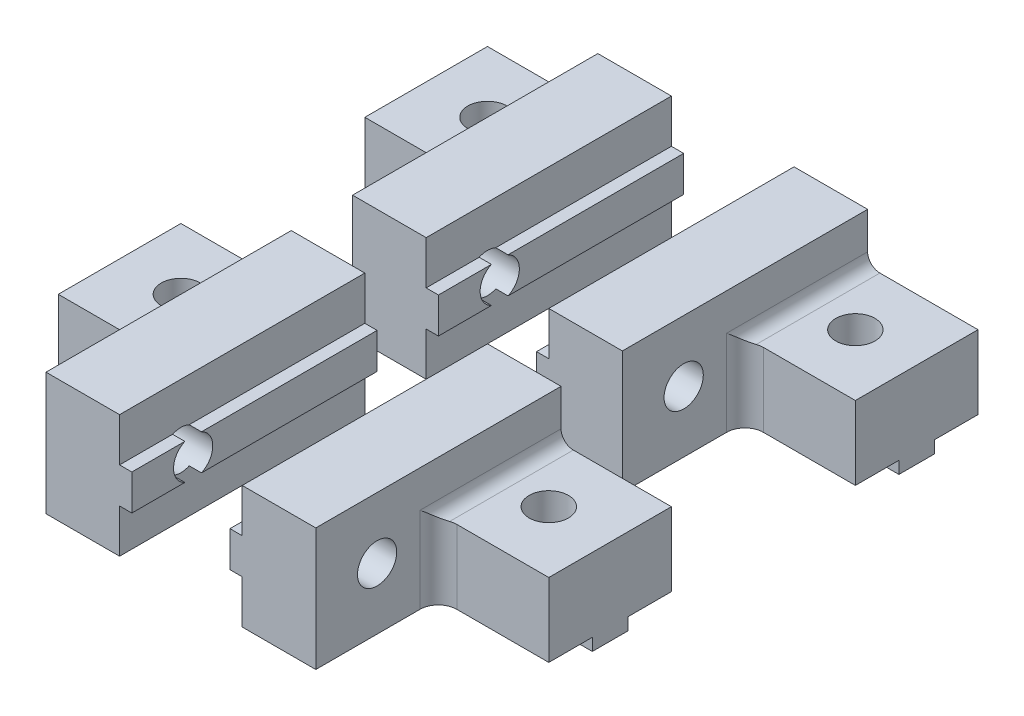
SolidWorks part; units mm, degrees
ref_plane "Front Plane" through (0, 0, 0) normal (0, 0, 1) x (1, 0, 0)
ref_plane "Top Plane" through (0, 0, 0) normal (0, 1, 0) x (1, 0, 0)
ref_plane "Right Plane" through (0, 0, 0) normal (1, 0, 0) x (0, 0, -1)
sketch "Esquisse1" plane through (0, 0, 0) normal (0, 0, 1) x (1, 0, 0)
  line L0 (0, 0) -> (15, 0)
  line L1 (15, 0) -> (15, 6)
  line L2 (15, 6) -> (7, 6)
  line L3 (6, 10) -> (6, 7)
  line L5 (6, 10) -> (0, 10)
  line L6 (0, 10) -> (0, 0)
  arc A0 (7, 6) -> (6, 7) centre (7, 7) cw
  point P5 (0, 0)
  point P9 (4.8458, 8.4496)
  dimension "D1" = 8
  dimension "D2" = 10
  dimension "D3" = 6
  dimension "D4" = 15
extrude "Main" add sketch "Esquisse1" along normal blind 20
sketch "Esquisse4" plane through (0, 0, 0) normal (-1, 0, 0) x (0, 0, 1)
  line L0 (20, 10) -> (0, 10) construction
  line L1 (0, 6.45) -> (20, 6.45)
  line L2 (0, 6.45) -> (0, 3.55)
  line L3 (0, 3.55) -> (20, 3.55)
  line L4 (20, 6.45) -> (20, 3.55)
  line L6 (0, 10) -> (0, 0) construction
  line L7 (20, 10) -> (20, 0) construction
  dimension "D1" = 2.9
  dimension "D2" = 3.55
extrude "VerticalGuidance" add sketch "Esquisse4" along normal blind 1
sketch "Esquisse2" plane through (0, 0, 0) normal (-1, 0, 0) x (0, 0, 1)
  line L0 (20, 10) -> (20, 6.45) construction
  line L5 (20, 0) -> (0, 0) construction
  circle A0 centre (15, 5) radius 1.6
  dimension "D1" = 3.2
  dimension "D2" = 5
  dimension "D3" = 5
extrude "VerticalHole" cut sketch "Esquisse2" against normal through all both and the other way through all
sketch "Esquisse5" plane through (0, 0, 0) normal (0, -1, 0) x (-1, 0, 0)
  line L1 (0, -3.55) -> (-15, -3.55)
  line L2 (0, -3.55) -> (0, -6.45)
  line L3 (0, -6.45) -> (-15, -6.45)
  line L4 (-15, -3.55) -> (-15, -6.45)
  line L8 (0, 0) -> (0, -14.3236) construction
  line L9 (-15, -20) -> (-15, 0) construction
  line L10 (0, 0) -> (-15, 0) construction
  dimension "D1" = 2.9
  dimension "D2" = 3.55
extrude "HorizontalGuidance" add sketch "Esquisse5" along normal blind 1
sketch "Esquisse3" plane through (0, 6, 0) normal (0, -1, 0) x (1, 0, 0)
  line L5 (15, 20) -> (15, 16.249) construction
  line L8 (15, 0) -> (7, 0) construction
  circle A0 centre (10, 5) radius 1.6
  dimension "D1" = 5
  dimension "D2" = 5
  dimension "D3" = 3.2
extrude "HorizontalHole" cut sketch "Esquisse3" against normal through all both and the other way through all
sketch "Esquisse9" plane through (0, 6, 0) normal (0, 1, 0) x (1, 0, 0)
  line L0 (15, -20) -> (15, -16.249) construction
  line L1 (6, -20) -> (15, -20)
  line L2 (6, -20) -> (6, -10)
  line L3 (6, -10) -> (15, -10)
  line L4 (15, -20) -> (15, -10)
  line L5 (15, 0) -> (7, 0) construction
  line L6 (6, -20) -> (6, 0) construction
  point P9 (4.1897, -20.9641)
  point P10 (15, -20)
  point P12 (4.6844, -20)
  point P13 (3.1848, -10)
  dimension "D1" = 10
extrude "Enlèv. mat.-Extru.4" cut sketch "Esquisse9" against normal through all both and the other way through all
fillet "Congé2" radius 1.5 1 edges at (6, 3.5, 10)
ref_plane "SymetryPlan" through (-5, 0, 0) normal (1, 0, 0) x (0, 0, -1)
ref_axis "Axe1" through (-5, 0, -4.75) along (0, 0, 1)
pattern_linear "Répétition linéaire1" count 2 spacing 25 along (0, 0, 1) of bodies 113 114
mirror "Symétrie3" about plane through (-5, 0, 0) normal (1, 0, 0) of bodies 115 113 116 117
